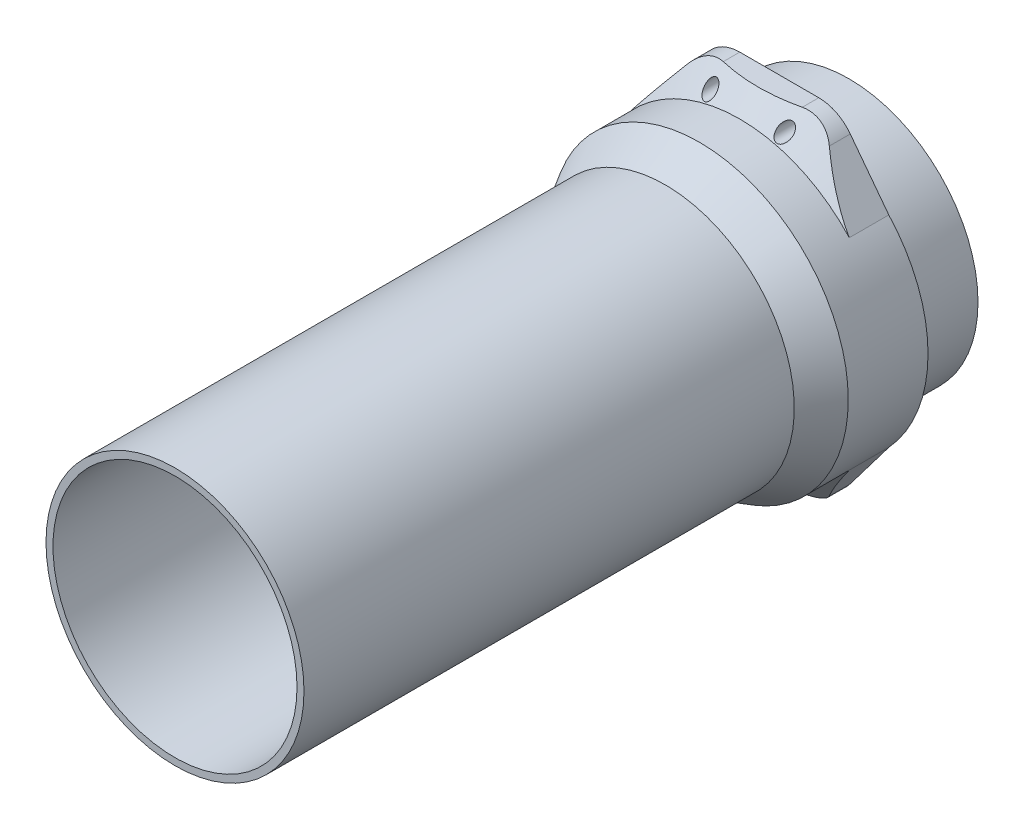
SolidWorks part; units mm, degrees
ref_plane "Front Plane" through (0, 0, 0) normal (0, 0, 1) x (1, 0, 0)
ref_plane "Top Plane" through (0, 0, 0) normal (0, 1, 0) x (1, 0, 0)
ref_plane "Right Plane" through (0, 0, 0) normal (1, 0, 0) x (0, 0, -1)
sketch "Sketch1" plane through (0, 0, 0) normal (0, 0, 1) x (1, 0, 0)
  circle A0 centre (0, 0) radius 52.5
  circle A1 centre (0, 0) radius 55.5
  dimension "D1" = 105
  dimension "D2" = 3
extrude "Boss-Extrude1" add sketch "Sketch1" along normal blind 290
sketch "Sketch2" plane through (0, 0, 0) normal (1, 0, 0) x (0, 0, -1)
  line L0 (0, 0) -> (-63, 55.5)
  line L1 (0, 55.5) -> (-290, 55.5) construction
  line L2 (-63, 55.5) -> (0, 55.5)
  line L3 (0, 55.5) -> (0, 0)
  line L4 (0, 0) -> (-63, -55.5)
  line L5 (-290, -55.5) -> (0, -55.5) construction
  line L6 (-63, -55.5) -> (0, -55.5)
  line L7 (0, -55.5) -> (0, 55.5) construction
  line L8 (0, -55.5) -> (0, 0)
  dimension "D1" = 63
extrude "Cut-Extrude1" [suppressed] cut sketch "Sketch2" against normal blind 300 and the other way blind 300 contours L3 L2 L0 | L6 L8 L4
ref_plane "Plane1" through (0, 0, 30) normal (0, 0, -1) x (-1, 0, 0)
sketch "Sketch4" plane through (0, 0, 30) normal (0, 0, -1) x (-1, 0, 0)
  circle A0 centre (0, 0) radius 64
  circle A1 centre (0, 0) radius 55.5 construction
  circle A2 centre (0, 0) radius 55.5
  dimension "D1" = 128
extrude "Boss-Extrude2" add sketch "Sketch4" against normal blind 30
sketch "Sketch5" plane through (0, 0, 30) normal (0, 0, -1) x (-1, 0, 0)
  line L0 (-25, 58.9152) -> (-25, 71.9152)
  line L1 (-25, 71.9152) -> (25, 71.9152)
  line L2 (25, 71.9152) -> (25, 58.9152)
  line L3 (-16, 65.4152) -> (16, 65.4152) construction
  line L4 (-25, 0) -> (25, 0) construction
  line L5 (-16, -65.4152) -> (16, -65.4152) construction
  line L6 (25, -71.9152) -> (25, -58.9152)
  line L7 (-25, -71.9152) -> (25, -71.9152)
  line L8 (-25, -58.9152) -> (-25, -71.9152)
  circle A0 centre (0, 0) radius 64 construction
  circle A1 centre (-16, 65.4152) radius 1.5
  circle A2 centre (16, 65.4152) radius 1.5
  arc A3 (-25, 58.9152) -> (25, 58.9152) centre (0, 0) cw
  arc A4 (-25, -58.9152) -> (25, -58.9152) centre (0, 0) ccw
  circle A5 centre (16, -65.4152) radius 1.5
  circle A6 centre (-16, -65.4152) radius 1.5
  point P5 (0, 71.9152)
  point P12 (0, 65.4152)
  point P18 (0, 0)
  dimension "D3" = 3
  dimension "D4" = 3
  dimension "D1" = 50
  dimension "D2" = 13
  dimension "D5" = 6.5
  dimension "D6" = 32
extrude "Boss-Extrude3" add sketch "Sketch5" against normal blind 4
chamfer "Chamfer1" distance 24 angle 43 4 edges at (-25, 58.9152, 32) (25, 58.9152, 32) (25, -58.9152, 32) (-25, -58.9152, 32) first distance on face at (-25, 65.4152, 32) first distance on face at (25, 65.4152, 32) first distance on face at (25, -65.4152, 32) first distance on face at (-25, -65.4152, 32)
fillet "Fillet1" radius 17 4 edges at (25.4436, -71.9152, 32) (-25.4436, -71.9152, 32) (-25.4436, 71.9152, 32) (25.4436, 71.9152, 32)
chamfer "Chamfer2" distance 13 angle 45 2 edges at (0, 64, 34) (0, -64, 34)
ref_plane "Plane2" through (0, 0, 34) normal (0, 0, -1) x (-1, 0, 0)
sketch "Sketch6" plane through (0, 0, 34) normal (0, 0, -1) x (-1, 0, 0)
  circle A0 centre (-16, 65.4152) radius 2.95
  circle A1 centre (16, 65.4152) radius 2.95
  circle A2 centre (-16, -65.4152) radius 2.95
  circle A3 centre (16, -65.4152) radius 2.95
  dimension "D1" = 5.9
extrude "Cut-Extrude2" cut sketch "Sketch6" against normal blind 14
chamfer "Chamfer3" distance 11 angle 60 1 edges at (-55.5, 0, 60) first distance on face at (-55.5, 0, 60)
